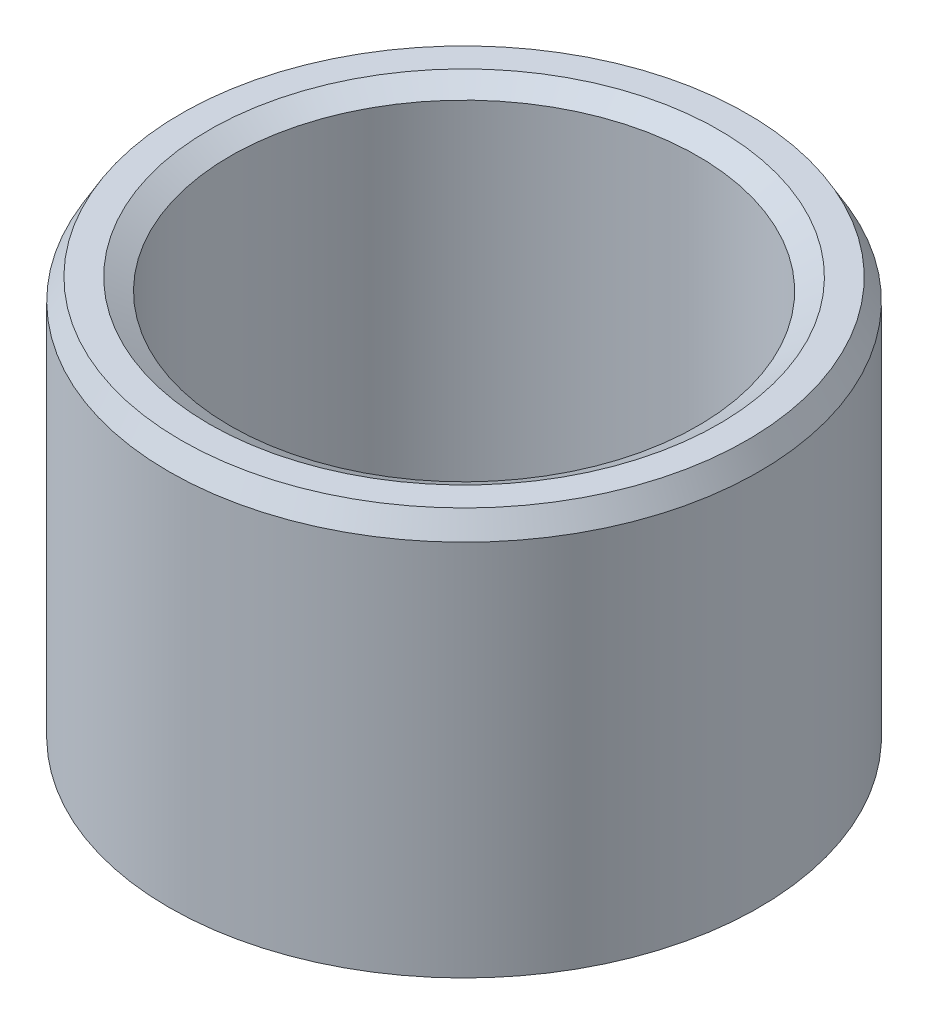
SolidWorks part; units mm, degrees
ref_plane "Front Plane" through (0, 0, 0) normal (0, 0, 1) x (1, 0, 0)
ref_plane "Top Plane" through (0, 0, 0) normal (0, 1, 0) x (1, 0, 0)
ref_plane "Right Plane" through (0, 0, 0) normal (1, 0, 0) x (0, 0, -1)
sketch "Sketch1" plane through (0, 0, 0) normal (0, 1, 0) x (1, 0, 0)
  circle A0 centre (0, 0) radius 45
  dimension "SLEEVE_OD" = 90
extrude "Boss-Extrude1" add sketch "Sketch1" along normal blind 62.6102
sketch "Sketch2" plane through (0, 0, 0) normal (0, 1, 0) x (1, 0, 0)
  circle A0 centre (0, 0) radius 35.6443
  dimension "BORE_D" = 71.2886
extrude "Cut-Extrude1" cut sketch "Sketch2" along normal through all
chamfer "Chamfer1" distance 3.2111 angle 30 4 edges at (0, 62.6102, 35.6443) (0, 0, 35.6443) (0, 0, 45) (0, 62.6102, 45) first distance on face at (0, 62.6102, 35.6443) first distance on face at (0, 0, 35.6443) first distance on face at (0, 62.6102, 45)
